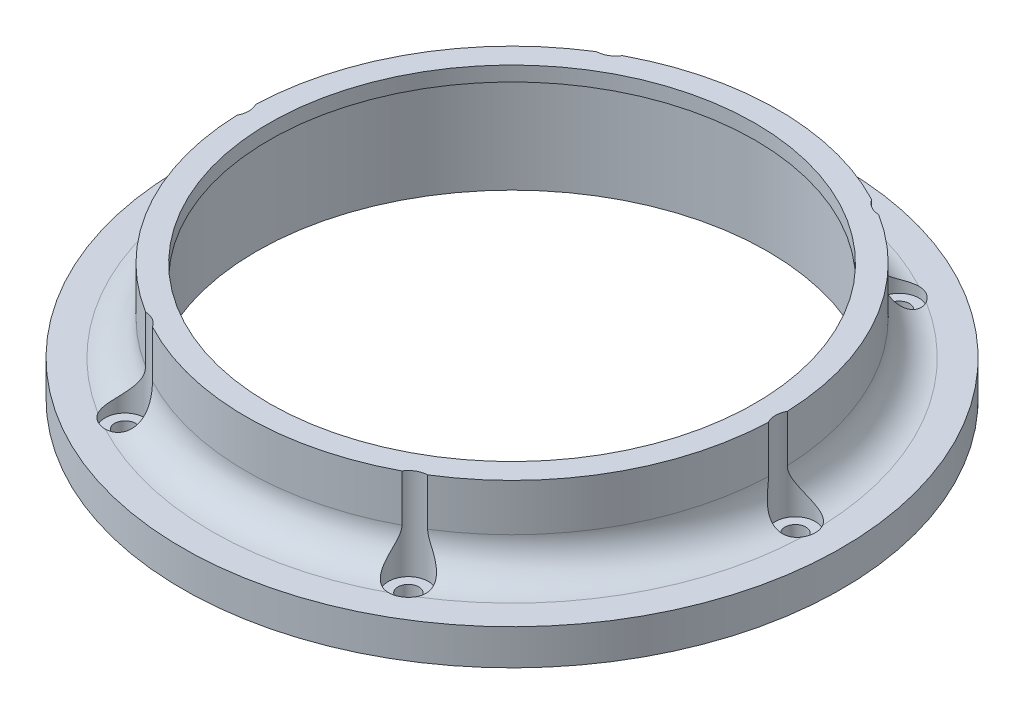
SolidWorks part; units mm, degrees
ref_plane "Front Plane" through (0, 0, 0) normal (0, 0, 1) x (1, 0, 0)
ref_plane "Top Plane" through (0, 0, 0) normal (0, 1, 0) x (1, 0, 0)
ref_plane "Right Plane" through (0, 0, 0) normal (1, 0, 0) x (0, 0, -1)
sketch "Sketch1" plane through (0, 0, 0) normal (0, 1, 0) x (1, 0, 0)
  circle A0 centre (0, 0) radius 61.25 construction
  circle A1 centre (0, 0) radius 55.25
  circle A2 centre (0, 0) radius 57.5
  dimension "D1" = 122.5
  dimension "D2" = 110.5
  dimension "D3" = 115
extrude "Boss-Extrude1" add sketch "Sketch1" along normal blind 22
sketch "Sketch2" plane through (0, 0, 0) normal (0, -1, 0) x (1, 0, 0)
  circle A0 centre (0, 0) radius 61.25 construction
  circle A1 centre (0, 0) radius 71.25
  circle A2 centre (0, 0) radius 57.5 construction
  circle A3 centre (0, 0) radius 57.5
  dimension "D1" = 122.5
  dimension "D2" = 10
extrude "Boss-Extrude2" add sketch "Sketch2" against normal blind 7.5
sketch "Sketch6" plane through (0, 7.5, 0) normal (0, 1, 0) x (1, 0, 0)
  circle A0 centre (0, 0) radius 61.25 construction
  point P0 (-61.25, 0)
  dimension "D1" = 122.5
hole_wizard "CBORE for M4 SBHCS1" positions "Sketch6" profile "Sketch5" counterbore size "M4" standard "ANSI Metric" end condition through all
sketch "Sketch5" plane through (-61.25, 7.5, 0) normal (1, 0, 0) x (0, 0, 1)
  line L0 (0, 0) -> (0, 7.5)
  line L1 (0, 7.5) -> (2.25, 7.5)
  line L3 (2.25, 7.5) -> (2.25, 2.2)
  line L4 (2.25, 2.2) -> (4.3, 2.2)
  line L5 (4.3, 2.2) -> (4.3, 0)
  line L7 (4.3, 0) -> (0, 0)
  line L11 (0, -6.35) -> (0, 107.95) construction
  dimension "Thru Hole Dia." = 4.5
  dimension "Thru Hole Depth" = 7.5
  dimension "C'Bore Dia." = 8.6
  dimension "C'Bore Depth" = 2.2
fillet "Fillet2" radius 7.5 1 edges at (57.5, 7.5, 0)
sketch "Sketch7" plane through (0, 7.5, 0) normal (0, 1, 0) x (1, 0, 0)
  circle A1 centre (-61.25, 0) radius 4.3
  circle A2 centre (-61.25, 0) radius 4.3
  dimension "D1" = 0
extrude "Cut-Extrude1" cut sketch "Sketch7" along normal through all
pattern_circular "CirPattern1" count 6 over 360 about axis through (0, 7.5, 0) along (0, -1, 0) of "Cut-Extrude1", "CBORE for M4 SBHCS1"
sketch "Sketch8" plane through (0, 22, 0) normal (0, 1, 0) x (1, 0, 0)
  circle A0 centre (0, 0) radius 52.5
  arc A12 (-57.4639, -2.0384) -> (-30.4972, -48.746) centre (0, 0) ccw
  arc A13 (-26.9666, -50.7844) -> (-30.4972, -48.746) centre (-30.625, -53.0441) ccw
  arc A14 (-26.9666, -50.7844) -> (26.9666, -50.7844) centre (0, 0) ccw
  arc A15 (30.4972, -48.746) -> (26.9666, -50.7844) centre (30.625, -53.0441) ccw
  arc A16 (30.4972, -48.746) -> (57.4639, -2.0384) centre (0, 0) ccw
  arc A17 (57.4639, 2.0384) -> (57.4639, -2.0384) centre (61.25, 0) ccw
  arc A18 (57.4639, 2.0384) -> (30.4972, 48.746) centre (0, 0) ccw
  arc A19 (26.9666, 50.7844) -> (30.4972, 48.746) centre (30.625, 53.0441) ccw
  arc A20 (26.9666, 50.7844) -> (-26.9666, 50.7844) centre (0, 0) ccw
  arc A21 (-30.4972, 48.746) -> (-26.9666, 50.7844) centre (-30.625, 53.0441) ccw
  arc A22 (-30.4972, 48.746) -> (-57.4639, 2.0384) centre (0, 0) ccw
  arc A23 (-57.4639, -2.0384) -> (-57.4639, 2.0384) centre (-61.25, 0) ccw
  arc A24 (-57.4639, -2.0384) -> (-30.4972, -48.746) centre (0, 0) ccw
  arc A25 (-26.9666, -50.7844) -> (-30.4972, -48.746) centre (-30.625, -53.0441) ccw
  arc A26 (-26.9666, -50.7844) -> (26.9666, -50.7844) centre (0, 0) ccw
  arc A27 (30.4972, -48.746) -> (26.9666, -50.7844) centre (30.625, -53.0441) ccw
  arc A28 (30.4972, -48.746) -> (57.4639, -2.0384) centre (0, 0) ccw
  arc A29 (57.4639, 2.0384) -> (57.4639, -2.0384) centre (61.25, 0) ccw
  arc A30 (57.4639, 2.0384) -> (30.4972, 48.746) centre (0, 0) ccw
  arc A31 (26.9666, 50.7844) -> (30.4972, 48.746) centre (30.625, 53.0441) ccw
  arc A32 (26.9666, 50.7844) -> (-26.9666, 50.7844) centre (0, 0) ccw
  arc A33 (-30.4972, 48.746) -> (-26.9666, 50.7844) centre (-30.625, 53.0441) ccw
  arc A34 (-30.4972, 48.746) -> (-57.4639, 2.0384) centre (0, 0) ccw
  arc A35 (-57.4639, -2.0384) -> (-57.4639, 2.0384) centre (-61.25, 0) ccw
  dimension "D2" = 5
  dimension "D1" = 0
extrude "Boss-Extrude3" add sketch "Sketch8" along normal blind 3.175
sketch "Sketch10" plane through (0, 0, 0) normal (0, -1, 0) x (1, 0, 0)
  circle A0 centre (0, 0) radius 55.25 construction
  circle A1 centre (0, 0) radius 71.25
  circle A2 centre (0, 0) radius 71.25
  circle A3 centre (61.25, 0) radius 2.25 construction
  circle A4 centre (30.625, 53.0441) radius 2.25 construction
  circle A5 centre (-30.625, 53.0441) radius 2.25 construction
  circle A6 centre (-61.25, 0) radius 2.25 construction
  circle A7 centre (-30.625, -53.0441) radius 2.25 construction
  circle A8 centre (30.625, -53.0441) radius 2.25 construction
  circle A9 centre (0, 0) radius 55.25
  circle A10 centre (61.25, 0) radius 2.25
  circle A11 centre (30.625, 53.0441) radius 2.25
  circle A12 centre (-30.625, 53.0441) radius 2.25
  circle A13 centre (-61.25, 0) radius 2.25
  circle A14 centre (-30.625, -53.0441) radius 2.25
  circle A15 centre (30.625, -53.0441) radius 2.25
  dimension "D1" = 0
extrude "Boss-Extrude4" add sketch "Sketch10" along normal blind 0.2
